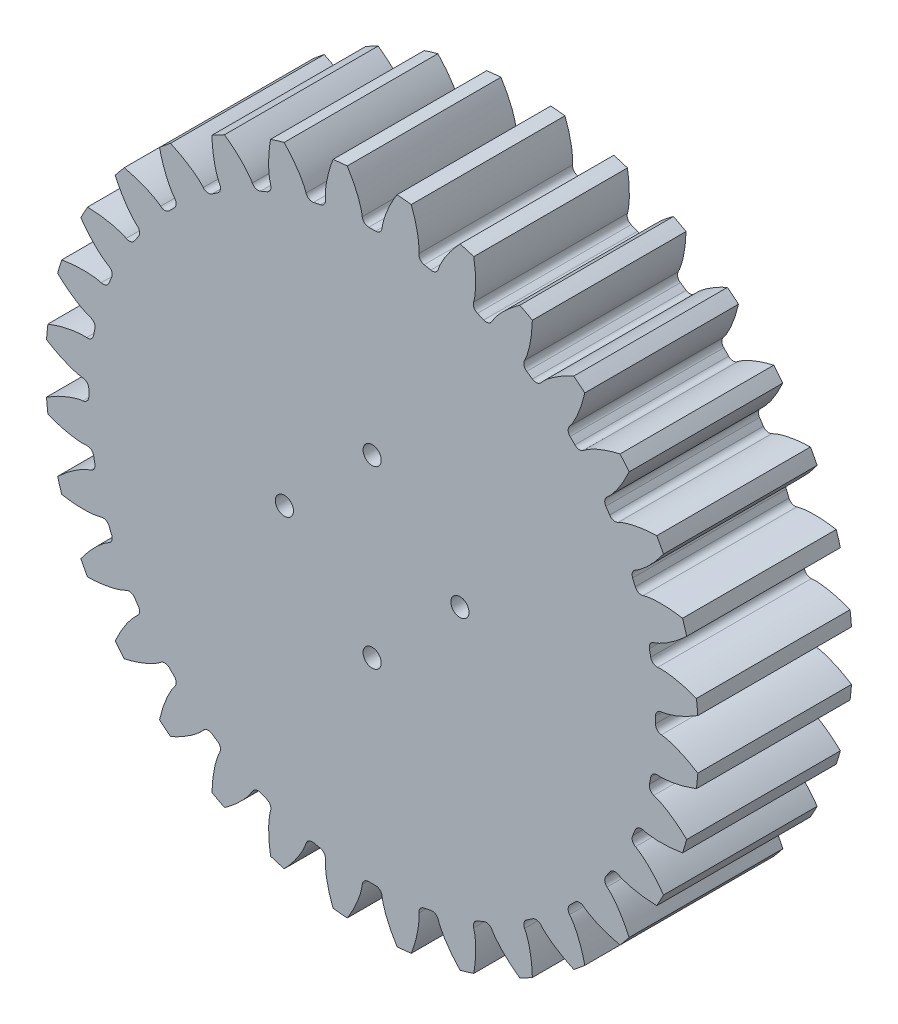
SolidWorks part; units mm, degrees
ref_plane "Front Plane" through (0, 0, 0) normal (0, 0, 1) x (1, 0, 0)
ref_plane "Top Plane" through (0, 0, 0) normal (0, 1, 0) x (1, 0, 0)
ref_plane "Right Plane" through (0, 0, 0) normal (1, 0, 0) x (0, 0, -1)
sketch "Sketch1" plane through (0, 0, 0) normal (0, 0, 1) x (1, 0, 0)
  line L0 (0, 0) -> (0, 25.4) construction
  line L1 (-8.1634, 28.3712) -> (8.1634, 22.4288) construction
  circle A0 centre (0, 0) radius 23.4156 construction
  circle A1 centre (0, 0) radius 26.9875 construction
  circle A2 centre (0, 0) radius 25.4 construction
  circle A3 centre (0, 0) radius 23.8682 construction
  circle A4 centre (0, 0) radius 3.175 construction
  circle A5 centre (0, 0) radius 6.35 construction
  point P8 (203.2, 0)
  point P13 (406.4, 0)
  dimension "OD | Outside Diameter" = 53.975
  dimension "Root Diameter" = 46.8312
  dimension "Gear Pitch Diameter" = 50.8
  dimension "Base Diameter" = 47.7364
  dimension "For Shaft Diameter" = 6.35
  dimension "Hub Diameter" = 12.7
  dimension "Pressure Angle" = 20
  dimension "Number of Teeth" = 812.8
  dimension "Gear Pitch | Diametral Pitch" = 406.4
sketch "Sketch2" plane through (0, 0, 0) normal (1, 0, 0) x (0, 0, -1)
  line L0 (-6.35, 0) -> (6.35, 0) construction
  line L1 (-6.35, 26.9875) -> (6.35, 26.9875) construction
  point P2 (0, 26.9875)
  point P4 (-5.715, 0)
  point P6 (-5.715, 26.9875)
  dimension "Overall Width" = 12.7
  dimension "Face Width" = 12.065
sketch "Sketch3" plane through (0, 0, 0) normal (0, 0, 1) x (1, 0, 0)
  circle A0 centre (0, 0) radius 26.9875
  circle A1 centre (0, 0) radius 26.9875 construction
extrude "Boss-Extrude1" add sketch "Sketch3" against normal up to vertex (6.35 mm away) and the other way up to vertex (6.35 mm away) up to point (0, 0, -6.35) other way up to point (0, 0, 6.35)
sketch "Sketch4" plane through (0, 0, 0) normal (0, 0, 1) x (1, 0, 0)
  line L0 (0, 0) -> (23.4019, 0.8003) construction
  line L2 (0, 0) -> (23.4019, -0.8003) construction
  line L4 (23.4019, 0.8003) -> (23.8542, 0.8157)
  line L5 (23.8542, -0.8157) -> (23.4019, -0.8003)
  arc A0 (23.4019, 0.8003) -> (23.4019, -0.8003) centre (0, 0) cw
  arc A3 (26.9089, 2.0577) -> (26.9089, -2.0577) centre (0, 0) cw
  circle A4 centre (0, 0) radius 26.9875 construction
  spline S0 degree 4 poles (23.8542, 0.8157) (23.8592, 0.816) (23.8729, 0.8167) (23.8989, 0.8189) (23.9413, 0.8234) (23.9952, 0.8305) (24.0647, 0.8414) (24.1465, 0.8562) (24.2362, 0.8746) (24.3337, 0.897) (24.4306, 0.9214) (24.5272, 0.9477) (24.6232, 0.9756) (24.7393, 1.0114) (24.8782, 1.0572) (25.04, 1.1149) (25.2228, 1.1851) (25.4085, 1.2619) (25.5905, 1.3418) (25.7737, 1.4274) (25.9504, 1.5136) (26.1331, 1.6083) (26.3013, 1.6982) (26.4888, 1.8044) (26.6399, 1.8918) (26.838, 2.0129) (26.9547, 2.0862) (27.0909, 2.1739) (27.1512, 2.214) (27.1883, 2.2386) knots 0 0 0 0 0 0.005377 0.015084 0.028532 0.04661 0.064855 0.092111 0.119476 0.146842 0.174209 0.201575 0.228941 0.256307 0.307035 0.361767 0.4165 0.471232 0.525964 0.580697 0.635429 0.690161 0.744894 0.799626 0.854358 0.909091 0.954545 1 1 1 1 1 construction
  spline S1 degree 4 poles (23.8542, 0.8157) (23.8592, 0.816) (23.8729, 0.8167) (23.8989, 0.8189) (23.9413, 0.8234) (23.9952, 0.8305) (24.0647, 0.8414) (24.1465, 0.8562) (24.2362, 0.8746) (24.3337, 0.897) (24.4306, 0.9214) (24.5272, 0.9477) (24.6232, 0.9756) (24.7393, 1.0114) (24.8782, 1.0572) (25.04, 1.1149) (25.2228, 1.1851) (25.4085, 1.2619) (25.5905, 1.3418) (25.7737, 1.4274) (25.9504, 1.5136) (26.1331, 1.6083) (26.3013, 1.6982) (26.4888, 1.8044) (26.6399, 1.8918) (26.7951, 1.9866) (26.8705, 2.0335) (26.9089, 2.0577) knots 0 0 0 0 0 0.005377 0.015084 0.028532 0.04661 0.064855 0.092111 0.119476 0.146842 0.174209 0.201575 0.228941 0.256307 0.307035 0.361767 0.4165 0.471232 0.525964 0.580697 0.635429 0.690161 0.744894 0.799626 0.854358 0.909091 0.909091 0.909091 0.909091 0.909091
  spline S2 degree 4 poles (23.8542, -0.8157) (23.8592, -0.816) (23.8729, -0.8167) (23.8989, -0.8189) (23.9413, -0.8234) (23.9952, -0.8305) (24.0647, -0.8414) (24.1465, -0.8562) (24.2362, -0.8746) (24.3337, -0.897) (24.4306, -0.9214) (24.5272, -0.9477) (24.6232, -0.9756) (24.7393, -1.0114) (24.8782, -1.0572) (25.04, -1.1149) (25.2228, -1.1851) (25.4085, -1.2619) (25.5905, -1.3418) (25.7737, -1.4274) (25.9504, -1.5136) (26.1331, -1.6083) (26.3013, -1.6982) (26.4888, -1.8044) (26.6399, -1.8918) (26.838, -2.0129) (26.9547, -2.0862) (27.0909, -2.1739) (27.1512, -2.214) (27.1883, -2.2386) knots 0 0 0 0 0 0.005377 0.015084 0.028532 0.04661 0.064855 0.092111 0.119476 0.146842 0.174209 0.201575 0.228941 0.256307 0.307035 0.361767 0.4165 0.471232 0.525964 0.580697 0.635429 0.690161 0.744894 0.799626 0.854358 0.909091 0.954545 1 1 1 1 1 construction
  spline S3 degree 4 poles (23.8542, -0.8157) (23.8592, -0.816) (23.8729, -0.8167) (23.8989, -0.8189) (23.9413, -0.8234) (23.9952, -0.8305) (24.0647, -0.8414) (24.1465, -0.8562) (24.2362, -0.8746) (24.3337, -0.897) (24.4306, -0.9214) (24.5272, -0.9477) (24.6232, -0.9756) (24.7393, -1.0114) (24.8782, -1.0572) (25.04, -1.1149) (25.2228, -1.1851) (25.4085, -1.2619) (25.5905, -1.3418) (25.7737, -1.4274) (25.9504, -1.5136) (26.1331, -1.6083) (26.3013, -1.6982) (26.4888, -1.8044) (26.6399, -1.8918) (26.7951, -1.9866) (26.8705, -2.0335) (26.9089, -2.0577) knots 0 0 0 0 0 0.005377 0.015084 0.028532 0.04661 0.064855 0.092111 0.119476 0.146842 0.174209 0.201575 0.228941 0.256307 0.307035 0.361767 0.4165 0.471232 0.525964 0.580697 0.635429 0.690161 0.744894 0.799626 0.854358 0.909091 0.909091 0.909091 0.909091 0.909091
  dimension "D1" = 46.8312
extrude "Cut-Extrude1" cut sketch "Sketch4" against normal through all both and the other way through all
fillet "Fillet1" radius 0.5326 2 edges at (23.4019, -0.8003, 0) (23.4019, 0.8003, 0)
pattern_circular "CirPattern1" count 32 over 360 about axis through (0, 0, 6.35) along (0, 0, -1) of "Cut-Extrude1", "Fillet1"
sketch "Sketch6" plane through (0, 0, 0) normal (0, 1, 0) x (1, 0, 0)
  line L0 (0, 10.0524) -> (0, -11.762) construction
sketch "Sketch7" plane through (0, 0, 0) normal (0, 0, 1) x (1, 0, 0)
  circle A0 centre (7.25, 0) radius 0.75
  dimension "D2" = 1.5
  dimension "D1" = 7.25
extrude "Cut-Extrude2" cut sketch "Sketch7" against normal through all both and the other way through all
pattern_circular "CirPattern2" count 4 every 90 about axis through (0, 0, -10.0524) along (0, 0, 1) of "Cut-Extrude2"
equation "\"Root Diameter@Sketch1\"=\"Root Diameter\""
equation "\"OD | Outside Diameter@Sketch1\"=\"Outside Diameter\""
equation "\"D1@CirPattern1\"=\"Number of Teeth\""
equation "\"Diametral Pitch\"= 16"
equation "\"Number of Teeth\"= 32"
equation "\"Pressure Angle\"=20"
equation "\"Pitch Diameter\"= \"Number of Teeth\" / \"Diametral Pitch\""
equation "\"Base Diameter\"= \"Pitch Diameter\" * cos ( \"Pressure Angle\" )"
equation "\"Outside Diameter\"= ( \"Number of Teeth\" + 2 ) / \"Diametral Pitch\""
equation "\"Dedendum\"= 1.25 / \"Diametral Pitch\""
equation "\"Root Diameter\"= \"Pitch Diameter\" - ( 2 * \"Dedendum\" )"
equation "\"Pitch Angle\"= 360deg / \"Number of Teeth\""
equation "\"Alpha\"= sqr ( \"Pitch Diameter\" ^ 2 - \"Base Diameter\" ^ 2 ) / \"Base Diameter\" * 180 / PI - \"Pressure Angle\""
equation "\"Beta\"= ( \"Pitch Angle\" / 4 - \"Alpha\" )"
equation "\"Phi\"= sqr ( ( \"Outside Diameter\" / 2 ) ^ 2 - ( \"Base Diameter\" / 2 ) ^ 2 ) / ( \"Base Diameter\" / 2 )"
equation "\"Addendum\"= 1 / \"Diametral Pitch\""
equation "\"WorkingDepth\"= 2 / \"Diametral Pitch\""
equation "\"WholeDepth\"= 2.25 / \"Diametral Pitch\""
equation "\"Clearance\"= 0.25 / \"Diametral Pitch\""
equation "\"ToothThickness\"= ( pi * 2 ) / \"Diametral Pitch\""
equation "\"CircularPitch\"= pi / \"Diametral Pitch\""
equation "\"Number of Teeth@Sketch1\"=\"Number of Teeth\""
equation "\"Gear Pitch | Diametral Pitch@Sketch1\"=\"Diametral Pitch\""
equation "\"Pressure Angle@Sketch1\"=\"Pressure Angle\""
equation "\"Gear Pitch Diameter@Sketch1\"=\"Pitch Diameter\""
equation "\"Base Diameter@Sketch1\"=\"Base Diameter\""
equation "\"Fillet\"= \"Clearance\" * cos ( \"Pressure Angle\" ) * tan ( ( 90 + \"Pressure Angle\" ) / 2 )"
equation "\"D1@Fillet1\"=\"Fillet\""
equation "\"D1@Sketch4\"=if( \"Base Diameter\">\"Root Diameter\",\"Root Diameter\",\"Base Diameter\"-.00001)"
equation "\"D1@Fillet2\"=\"Fillet\""
equation "\"D1@Sketch7\"=7.25mm"
equation "\"D2@Sketch7\"=1.5mm"
